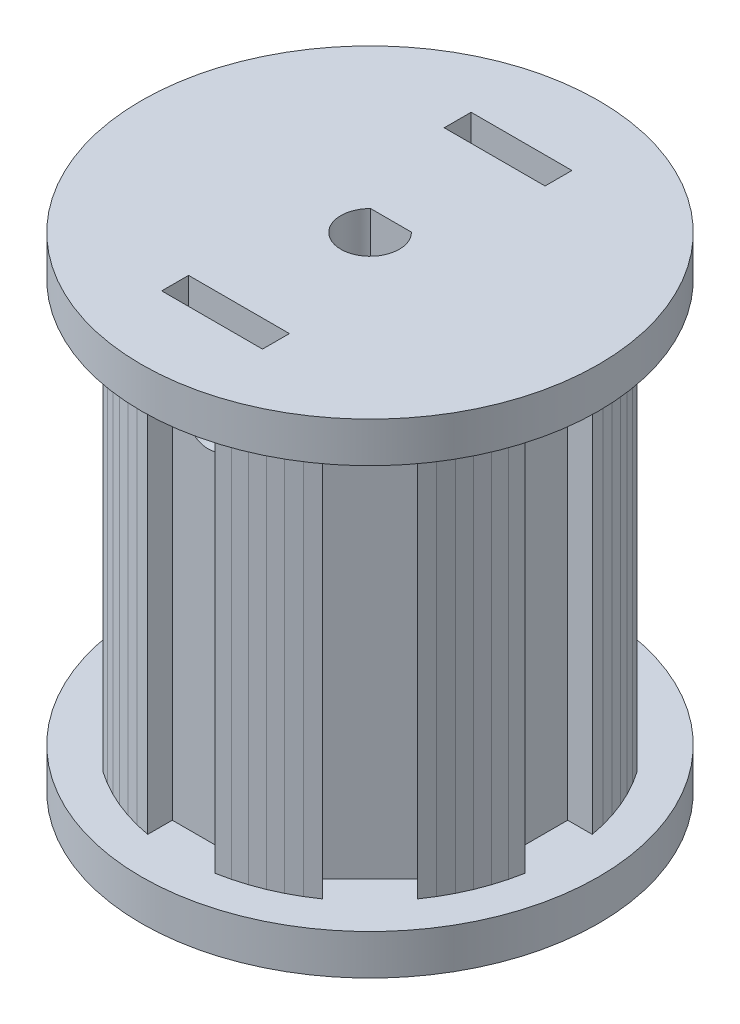
SolidWorks part; units mm, degrees
ref_plane "Front Plane" through (0, 0, 0) normal (0, 0, 1) x (1, 0, 0)
ref_plane "Top Plane" through (0, 0, 0) normal (0, 1, 0) x (1, 0, 0)
ref_plane "Right Plane" through (0, 0, 0) normal (1, 0, 0) x (0, 0, -1)
ref_plane "Plane1" through (0, -15, 0) normal (0, 1, 0) x (1, 0, 0)
ref_plane "Plane2" through (0, 21, 0) normal (0, 1, 0) x (1, 0, 0)
sketch "Sketch1" plane through (0, -15, 0) normal (0, 1, 0) x (1, 0, 0)
  circle A0 centre (0, 0) radius 17
  dimension "D1" = 34
extrude "Boss-Extrude1" add sketch "Sketch1" along normal blind 3
sketch "Sketch3" plane through (0, 21, 0) normal (0, 1, 0) x (1, 0, 0)
  circle A0 centre (0, 0) radius 17
  dimension "D1" = 34
extrude "Boss-Extrude2" add sketch "Sketch3" against normal blind 3 separate body
ref_plane "Plane3" through (0, -12, 0) normal (0, 1, 0) x (1, 0, 0)
sketch "Sketch6" plane through (0, -12, 0) normal (0, 1, 0) x (1, 0, 0)
  line L0 (-10.3961, -6.8606) -> (-11.6878, -8.1522)
  line L1 (-11.6878, -8.1522) -> (-12.2448, -7.2889)
  line L2 (-12.2448, -7.2889) -> (-12.7381, -6.3877)
  line L3 (-12.7381, -6.3877) -> (-13.1653, -5.4532)
  line L4 (-13.1653, -5.4532) -> (-13.524, -4.4905)
  line L5 (-13.524, -4.4905) -> (-13.8124, -3.5043)
  line L6 (-13.8124, -3.5043) -> (-14.029, -2.5)
  line L7 (-14.029, -2.5) -> (-12.2023, -2.5)
  line L8 (-12.2023, -2.5) -> (-12.2023, 2.5)
  line L9 (-12.2023, 2.5) -> (-14.029, 2.5)
  line L10 (-14.029, 2.5) -> (-13.8124, 3.5043)
  line L11 (-13.8124, 3.5043) -> (-13.524, 4.4905)
  line L12 (-13.524, 4.4905) -> (-13.1653, 5.4532)
  line L13 (-13.1653, 5.4532) -> (-12.7381, 6.3877)
  line L14 (-12.7381, 6.3877) -> (-12.2448, 7.2889)
  line L15 (-12.2448, 7.2889) -> (-11.6878, 8.1522)
  line L16 (-11.6878, 8.1522) -> (-10.3961, 6.8606)
  line L17 (-10.3961, 6.8606) -> (-6.8606, 10.3961)
  line L18 (-6.8606, 10.3961) -> (-8.1522, 11.6878)
  line L19 (-8.1522, 11.6878) -> (-7.2889, 12.2448)
  line L20 (-7.2889, 12.2448) -> (-6.3877, 12.7381)
  line L21 (-6.3877, 12.7381) -> (-5.4532, 13.1653)
  line L22 (-5.4532, 13.1653) -> (-4.4905, 13.524)
  line L23 (-4.4905, 13.524) -> (-3.5043, 13.8124)
  line L24 (-3.5043, 13.8124) -> (-2.5, 14.029)
  line L25 (-2.5, 14.029) -> (-2.5, 12.1742)
  line L26 (-2.5, 12.1742) -> (2.5, 12.2023)
  line L27 (2.5, 12.2023) -> (2.5, 14.029)
  line L28 (2.5, 14.029) -> (3.5043, 13.8124)
  line L29 (3.5043, 13.8124) -> (4.4905, 13.524)
  line L30 (4.4905, 13.524) -> (5.4532, 13.1653)
  line L31 (5.4532, 13.1653) -> (6.3877, 12.7381)
  line L32 (6.3877, 12.7381) -> (7.2889, 12.2448)
  line L33 (7.2889, 12.2448) -> (8.1522, 11.6878)
  line L34 (8.1522, 11.6878) -> (6.8606, 10.3961)
  line L35 (6.8606, 10.3961) -> (10.3961, 6.8606)
  line L36 (10.3961, 6.8606) -> (11.6878, 8.1522)
  line L37 (11.6878, 8.1522) -> (12.2448, 7.2889)
  line L38 (12.2448, 7.2889) -> (12.7381, 6.3877)
  line L39 (12.7381, 6.3877) -> (13.1653, 5.4532)
  line L40 (13.1653, 5.4532) -> (13.524, 4.4905)
  line L41 (13.524, 4.4905) -> (13.8124, 3.5043)
  line L42 (13.8124, 3.5043) -> (14.029, 2.5)
  line L43 (14.029, 2.5) -> (12.2023, 2.5)
  line L44 (12.2023, 2.5) -> (12.2023, -2.5)
  line L45 (12.2023, -2.5) -> (14.029, -2.5)
  line L46 (14.029, -2.5) -> (13.8124, -3.5043)
  line L47 (13.8124, -3.5043) -> (13.524, -4.4905)
  line L48 (13.524, -4.4905) -> (13.1653, -5.4532)
  line L49 (13.1653, -5.4532) -> (12.7381, -6.3877)
  line L50 (12.7381, -6.3877) -> (12.2448, -7.2889)
  line L51 (12.2448, -7.2889) -> (11.6878, -8.1522)
  line L52 (11.6878, -8.1522) -> (10.3961, -6.8606)
  line L53 (10.3961, -6.8606) -> (6.8606, -10.3961)
  line L54 (6.8606, -10.3961) -> (8.1522, -11.6878)
  line L55 (8.1522, -11.6878) -> (7.2889, -12.2448)
  line L56 (7.2889, -12.2448) -> (6.3877, -12.7381)
  line L57 (6.3877, -12.7381) -> (5.4532, -13.1653)
  line L58 (5.4532, -13.1653) -> (4.4905, -13.524)
  line L59 (4.4905, -13.524) -> (3.5043, -13.8124)
  line L60 (3.5043, -13.8124) -> (2.5, -14.029)
  line L61 (2.5, -14.029) -> (2.5, -12.2023)
  line L62 (2.5, -12.2023) -> (-2.5, -12.2023)
  line L63 (-2.5, -12.2023) -> (-2.5, -14.029)
  line L64 (-2.5, -14.029) -> (-3.5043, -13.8124)
  line L65 (-3.5043, -13.8124) -> (-4.4905, -13.524)
  line L66 (-4.4905, -13.524) -> (-5.4532, -13.1653)
  line L67 (-5.4532, -13.1653) -> (-6.3877, -12.7381)
  line L68 (-6.3877, -12.7381) -> (-7.2889, -12.2448)
  line L69 (-7.2889, -12.2448) -> (-8.1522, -11.6878)
  line L70 (-8.1522, -11.6878) -> (-6.8606, -10.3961)
  line L71 (-6.8606, -10.3961) -> (-10.3961, -6.8606)
extrude "Boss-Extrude3" add sketch "Sketch6" along normal blind 31
sketch "Sketch7" plane through (-0.0686, 0, -12.1878) normal (-0.0056, 0, -1) x (-1, 0, 0.0056)
  line L0 (2.5686, 18) -> (-2.4313, 18) construction
  circle A0 centre (-0.1208, 15) radius 1.7514
  dimension "D1" = 3
extrude "Cut-Extrude11" cut sketch "Sketch7" against normal blind 50
sketch "Sketch2" plane through (0, -15, 0) normal (0, 1, 0) x (1, 0, 0)
  line L0 (1.5148, 1.5664) -> (-1.5212, 1.5664)
  arc A0 (1.5148, 1.5664) -> (-1.5212, 1.5664) centre (-0.0032, 0.0099) cw
  point P3 (1.7803, 1.4206)
  point P4 (-1.7023, 1.4206)
  point P5 (1.3987, 1.5664)
  point P6 (-1.3987, 1.5664)
  point P7 (1.5148, 1.5664)
  point P8 (-1.5212, 1.5664)
extrude "Cut-Extrude1" cut sketch "Sketch2" along normal blind 50
sketch "Sketch8" plane through (0, -15, 0) normal (0, 1, 0) x (1, 0, 0)
  line L1 (-3.9871, 11.5054) -> (3.5129, 11.5054)
  line L2 (-3.9871, 11.5054) -> (-3.9871, 9.5054)
  line L3 (-3.9871, 9.5054) -> (3.5129, 9.5054)
  line L4 (3.5129, 11.5054) -> (3.5129, 9.5054)
  dimension "D1" = 7.5
  dimension "D2" = 2
  dimension "D3" = 2
extrude "Cut-Extrude12" cut sketch "Sketch8" along normal blind 40
ref_plane "Plane4" through (0, 0, 0) normal (0, 0, 1) x (1, 0, 0)
mirror "Mirror1" about plane through (0, 0, 0) normal (0, 0, 1) of "Cut-Extrude12"
ref_plane "Plane5" through (0, 0, 0) normal (1, 0, 0) x (0, 0, -1)
